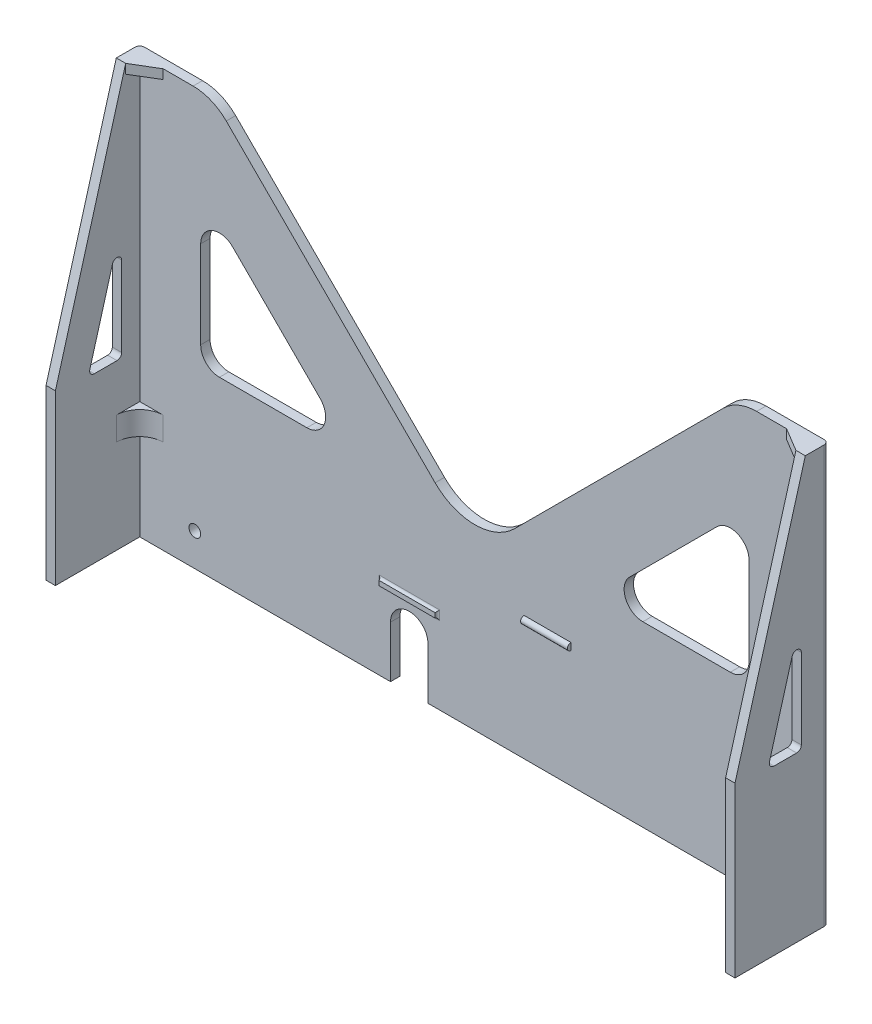
SolidWorks part; units mm, degrees
ref_plane "Plano frontal" through (0, 0, 0) normal (0, 0, 1) x (1, 0, 0)
ref_plane "Plano superior" through (0, 0, 0) normal (0, 1, 0) x (1, 0, 0)
ref_plane "Plano direito" through (0, 0, 0) normal (1, 0, 0) x (0, 0, -1)
sketch "Esboço6" plane through (0, -284.3476, 0) normal (0, 1, 0) x (1, 0, 0)
  line L0 (4.5, 12.6129) -> (2.5, 12.6129)
  line L1 (2.5, 2.1129) -> (2.5, 32.6129) construction
  line L2 (149.5, 12.6129) -> (147.5, 12.6129)
  line L4 (149.5, 12.6129) -> (149.5, 32.6129)
  line L5 (149.5, 32.6129) -> (2.5, 32.6129)
  line L6 (2.5, 12.6129) -> (2.5, 32.6129)
  line L7 (4.5, 4.1129) -> (4.5, 30.6129) construction
  line L8 (147.5, 4.1129) -> (147.5, 30.6129) construction
  line L14 (4.5, 12.6129) -> (4.5, 30.6129)
  line L15 (147.5, 30.6129) -> (4.5, 30.6129)
  line L16 (147.5, 12.6129) -> (147.5, 30.6129)
  line L17 (149.5, 2.1129) -> (149.5, 32.6129) construction
  line L18 (147.5, 4.1129) -> (4.5, 4.1129) construction
  line L19 (149.5, 2.1129) -> (2.5, 2.1129) construction
  point P8 (76, 17.5)
  dimension "D1" = 147
  dimension "D2" = 20
  dimension "D3" = 2
extrude "Ressalto-extrusão3" add sketch "Esboço6" along normal blind 89
fillet "Filete3" radius 1 2 edges at (149.5, -239.8476, -32.6129) (2.5, -239.8476, -32.6129)
sketch "Esboço16" plane through (0, 0, -30.6129) normal (0, 0, 1) x (1, 0, 0)
  line L0 (62, -284.3476) -> (62, -266.8476) construction
  line L1 (4.5, -284.3476) -> (147.5, -284.3476) construction
  line L3 (68, -266.3476) -> (56, -266.3476)
  line L4 (68, -266.3476) -> (68, -267.3476)
  line L5 (68, -267.3476) -> (56, -267.3476)
  line L6 (56, -266.3476) -> (56, -267.3476)
  line L7 (68, -266.3476) -> (56, -267.3476) construction
  line L8 (68, -267.3476) -> (56, -266.3476) construction
  line L9 (147.5, -195.3476) -> (147.5, -284.3476) construction
  point P8 (68, -266.8476)
  dimension "D1" = 17
  dimension "D2" = 1
  dimension "D3" = 12
  dimension "D4" = 79.5
extrude "Ressalto-extrusão5" add sketch "Esboço16" along normal blind 0.5
fillet "Filete7" radius 0.5 4 edges at (56, -266.8476, -30.6129) (68, -266.8476, -30.6129) (62, -266.3476, -30.6129) (62, -267.3476, -30.6129)
sketch "Esboço20" plane through (147.5, 0, 0) normal (-1, 0, 0) x (0, 0, 1)
  line L1 (-27.6129, -195.3476) -> (-12.6129, -195.3476)
  line L12 (-30.6129, -195.3476) -> (-12.6129, -195.3476) construction
  line L16 (-19.6048, -249.3476) -> (-26.7591, -249.3476) construction
  line L25 (-12.6129, -284.3476) -> (-31.6129, -284.3476) construction
  line L26 (-12.6129, -195.3476) -> (-12.6129, -284.3476) construction
  line L27 (-12.6129, -248.3476) -> (-27.6129, -195.3476)
  line L28 (-12.6129, -195.3476) -> (-12.6129, -248.3476)
  line L29 (-12.6129, -195.3476) -> (-31.6129, -195.3476) construction
  line L30 (-19.9649, -248.0753) -> (-24.7969, -231.0022)
  line L31 (-20.9271, -249.3476) -> (-25.7591, -249.3476)
  line L32 (-26.7591, -248.3476) -> (-26.7591, -231.2746)
  line L33 (-19.3484, -250.2539) -> (-34.3484, -197.2539) construction
  line L34 (-31.6129, -284.3476) -> (-31.6129, -195.3476) construction
  arc A3 (-26.7591, -248.3476) -> (-25.7591, -249.3476) centre (-25.7591, -248.3476) ccw
  arc A4 (-26.7591, -231.2746) -> (-24.7969, -231.0022) centre (-25.7591, -231.2746) cw
  arc A5 (-20.9271, -249.3476) -> (-19.9649, -248.0753) centre (-20.9271, -248.3476) ccw
  dimension "D2" = 35
  dimension "D4" = 1
  dimension "D1" = 15
  dimension "D3" = 7
  dimension "D5" = 53
  dimension "D6" = 4.8538
extrude "Corte-extrusão9" cut sketch "Esboço20" along normal blind 200 and the other way blind 10
sketch "Esboço22" plane through (0, 0, -30.6129) normal (0, 0, 1) x (1, 0, 0)
  line L0 (147.5, -195.3476) -> (4.5, -195.3476) construction
  line L1 (131.9706, -195.3476) -> (20.0294, -195.3476)
  line L2 (134.5, -223.6882) -> (134.5, -242.3476)
  line L3 (130.5, -246.3476) -> (111.8406, -246.3476)
  line L4 (17.5, -223.6882) -> (17.5, -242.3476)
  line L5 (147.5, -195.3476) -> (147.5, -284.3476) construction
  line L6 (4.5, -195.3476) -> (4.5, -284.3476) construction
  line L7 (147.5, -195.3476) -> (147.5, -284.3476) construction
  line L8 (84.4853, -242.8329) -> (131.9706, -195.3476)
  line L9 (67.5147, -242.8329) -> (20.0294, -195.3476)
  line L10 (131.9706, -195.3476) -> (20.0294, -195.3476)
  line L11 (42.9878, -239.5192) -> (24.3284, -220.8598)
  line L12 (109.0122, -239.5192) -> (127.6716, -220.8598)
  line L13 (76, -195.3476) -> (76, -35.7755) construction
  line L14 (4.5, -195.3476) -> (147.5, -195.3476) construction
  line L15 (40.1594, -246.3476) -> (21.5, -246.3476)
  line L16 (4.5, -284.3476) -> (147.5, -284.3476) construction
  line L18 (66, -284.3476) -> (58, -284.3476)
  line L19 (66, -284.3476) -> (66, -269.3476)
  line L20 (66, -269.3476) -> (58, -269.3476)
  line L21 (58, -284.3476) -> (58, -269.3476)
  arc A0 (67.5147, -242.8329) -> (84.4853, -242.8329) centre (76, -234.3476) ccw
  arc A1 (24.3284, -220.8598) -> (17.5, -223.6882) centre (21.5, -223.6882) ccw
  arc A2 (17.5, -242.3476) -> (21.5, -246.3476) centre (21.5, -242.3476) ccw
  arc A3 (40.1594, -246.3476) -> (42.9878, -239.5192) centre (40.1594, -242.3476) ccw
  arc A4 (111.8406, -246.3476) -> (109.0122, -239.5192) centre (111.8406, -242.3476) cw
  arc A5 (134.5, -242.3476) -> (130.5, -246.3476) centre (130.5, -242.3476) cw
  arc A6 (127.6716, -220.8598) -> (134.5, -223.6882) centre (130.5, -223.6882) cw
  circle A7 centre (16.25, -277.3476) radius 1.25
  circle A8 centre (135.75, -277.3476) radius 1.25
  point P19 (76, -251.3182)
  point P34 (49.8162, -246.3476)
  line M24 (147.5, -195.3476) -> (4.5, -195.3476)
  line M52 (4.5, -284.3476) -> (147.5, -284.3476)
  dimension "D4" = 12
  dimension "D7" = 4
  dimension "D9" = 7
  dimension "D6" = 7
  dimension "D11" = 2.5
  dimension "D12" = 2.5
  dimension "D15" = 50
  dimension "D18" = 4
  dimension "D19" = 4
  dimension "D20" = 4
  dimension "D1" = 13
  dimension "D2" = 13
  dimension "D3" = 15
  dimension "D8" = 11.75
  dimension "D5" = 15
  dimension "D10" = 11.75
  dimension "D13" = 8
  dimension "D14" = 81.5
  dimension "D16" = 90
  dimension "D17" = 15
extrude "Corte-extrusão10" cut sketch "Esboço22" against normal through all contours L9 A0 L8 M24 | A6 L12 A4 L3 A5 L2 | L15 A3 L11 A1 L4 A2 | A7 | A8 | L21 L19 L20 M52 | L13 L10 L9 A0 region at (76, -213.6705, -30.6129) region at (123.998, -235.8456, -30.6129) region at (28.002, -235.8456, -30.6129) region at (62, -276.8476, -30.6129) region at (16.25, -277.3476, -30.6129) region at (135.75, -277.3476, -30.6129)
sketch "Esboço25" plane through (0, -195.3476, 0) normal (0, 1, 0) x (1, 0, 0)
  line L0 (147.5, 30.6129) -> (142.5, 30.6129)
  line L1 (147.5, 30.6129) -> (131.9706, 30.6129) construction
  line L2 (142.5, 30.6129) -> (147.5, 27.6129)
  line L3 (147.5, 27.6129) -> (147.5, 30.6129)
  line L4 (4.5, 30.6129) -> (9.5, 30.6129)
  line L5 (20.0294, 30.6129) -> (4.5, 30.6129) construction
  line L6 (9.5, 30.6129) -> (4.5, 27.6129)
  line L7 (4.5, 27.6129) -> (4.5, 30.6129)
  line L8 (149.5, 27.6129) -> (147.5, 27.6129) construction
  line L9 (4.5, 27.6129) -> (2.5, 27.6129) construction
extrude "Ressalto-extrusão8" add sketch "Esboço25" against normal blind 2
fillet "Filete12" radius 10 2 edges at (20.0294, -195.3476, -31.6129) (131.9706, -195.3476, -31.6129)
fillet "Filete13" 2 edges at (66, -269.3476, -31.6129) (58, -269.3476, -31.6129) type full round first side face at (66, -276.8476, -31.6129) second side face at (58, -276.8476, -31.6129) middle face at (62, -269.3476, -31.6129)
sketch "Esboço30" plane through (0, 0, -30.6129) normal (0, 0, 1) x (1, 0, 0)
  line L0 (66, -284.3476) -> (147.5, -284.3476) construction
  line L1 (96.5, -257.8476) -> (86.5, -257.8476)
  line L2 (96.5, -257.8476) -> (96.5, -259.3476)
  line L3 (96.5, -259.3476) -> (86.5, -259.3476)
  line L4 (86.5, -257.8476) -> (86.5, -259.3476)
  line L5 (147.5, -197.3476) -> (147.5, -284.3476) construction
  dimension "D1" = 10
  dimension "D2" = 25
  dimension "D3" = 51
  dimension "D4" = 1.5
extrude "Ressalto-extrusão10" add sketch "Esboço30" along normal blind 0.75
fillet "Filete14" 2 edges at (91.5, -257.8476, -29.8629) (91.5, -259.3476, -29.8629) type full round first side face at (91.5, -257.8476, -30.2379) second side face at (91.5, -259.3476, -30.2379) middle face at (91.5, -258.5976, -29.8629)
sketch "Esboço31" plane through (0, -284.3476, 0) normal (0, -1, 0) x (1, 0, 0)
  line L0 (66, -30.6129) -> (147.5, -30.6129) construction
  line L1 (147.5, -30.6129) -> (142.5, -30.6129)
  line L2 (147.5, -30.6129) -> (147.5, -25.6129)
  line L6 (4.5, -30.6129) -> (9.5, -30.6129)
  line L7 (4.5, -30.6129) -> (4.5, -25.6129)
  arc A0 (147.5, -25.6129) -> (142.5, -30.6129) centre (142.5, -25.6129) cw
  arc A1 (4.5, -25.6129) -> (9.5, -30.6129) centre (9.5, -25.6129) ccw
extrude "Ressalto-extrusão11" add sketch "Esboço31" against normal blind 5 from offset 20 offset against normal yes
